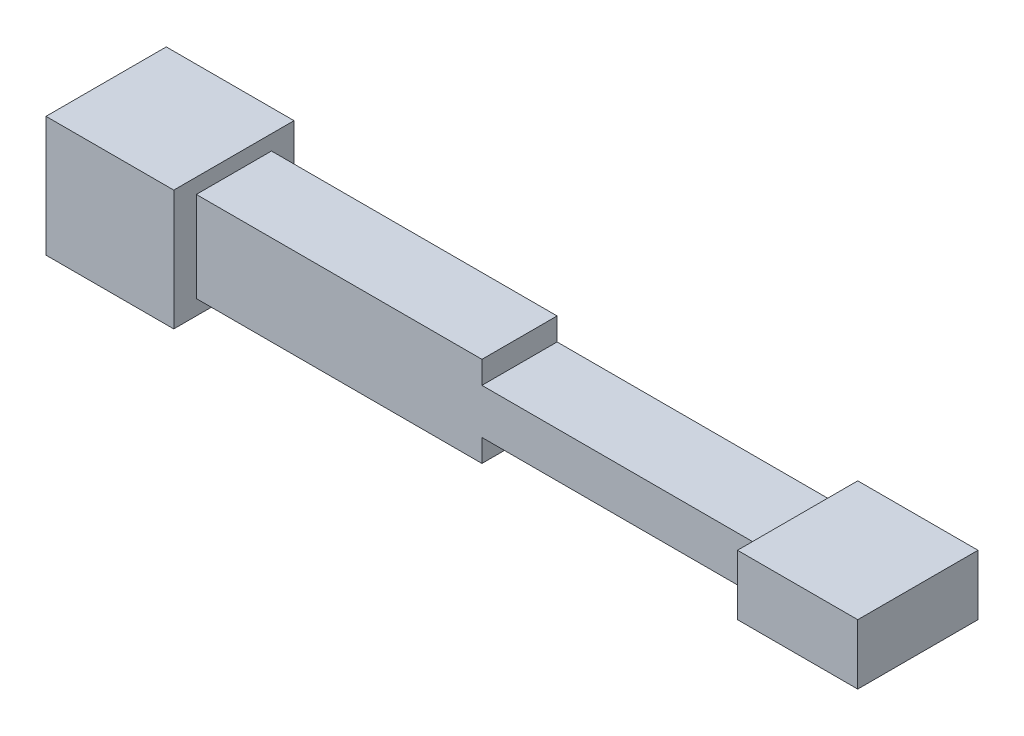
SolidWorks part; units mm, degrees
ref_plane "Front Plane" through (0, 0, 0) normal (0, 0, 1) x (1, 0, 0)
ref_plane "Top Plane" through (0, 0, 0) normal (0, 1, 0) x (1, 0, 0)
ref_plane "Right Plane" through (0, 0, 0) normal (1, 0, 0) x (0, 0, -1)
sketch "Sketch1" plane through (0, 0, 0) normal (0, 0, 1) x (1, 0, 0)
  line L0 (-54, 0) -> (54, 0) construction
  line L2 (54, -4) -> (38, -4)
  line L3 (54, -4) -> (54, 4)
  line L4 (54, 4) -> (38, 4)
  line L5 (38, -4) -> (38, 4)
  line L6 (54, -4) -> (38, 4) construction
  line L7 (54, 4) -> (38, -4) construction
  line L8 (-54, -8) -> (-37, -8)
  line L9 (-54, -8) -> (-54, 8)
  line L10 (-54, 8) -> (-37, 8)
  line L11 (-37, -8) -> (-37, 8)
  line L12 (-54, -8) -> (-37, 8) construction
  line L13 (-54, 8) -> (-37, -8) construction
  line L14 (-37, -6) -> (1, -6)
  line L15 (-37, -6) -> (-37, 6)
  line L16 (-37, 6) -> (1, 6)
  line L17 (1, -6) -> (1, 6)
  line L18 (-37, -6) -> (1, 6) construction
  line L19 (-37, 6) -> (1, -6) construction
  line L20 (1, -3) -> (38, -3)
  line L21 (1, -3) -> (1, 3)
  line L22 (1, 3) -> (38, 3)
  line L23 (38, -3) -> (38, 3)
  line L24 (1, -3) -> (38, 3) construction
  line L25 (1, 3) -> (38, -3) construction
  point P0 (46, 0)
  point P3 (54, 0)
  point P4 (0, 0)
  point P10 (-45.5, 0)
  point P15 (-54, 0)
  point P16 (-18, 0)
  point P21 (19.5, 0)
  point P26 (30.354, 0)
  point P27 (21.4286, 0)
  dimension "D1" = 8
  dimension "D2" = 16
  dimension "D3" = 108
  dimension "D4" = 16
  dimension "D5" = 17
  dimension "D6" = 12
  dimension "D7" = 38
  dimension "D8" = 6
extrude "Boss-Extrude1" add sketch "Sketch1" along normal mid plane 16 contours L8 L11 L10 L9 | L5 L2 L3 L4 region at (46, 0, 0) region at (-45.5, 0, 0)
extrude "Boss-Extrude2" add sketch "Sketch1<3>" along normal mid plane 10 contours L14 L17 L16 L11 | L22 L17 L20 L5 region at (19.5, 0, 0) region at (-18, 0, 0)
sketch "Sketch1<3>" plane through (0, 0, 0) normal (0, 0, 1) x (1, 0, 0) same geometry as "Sketch1"
